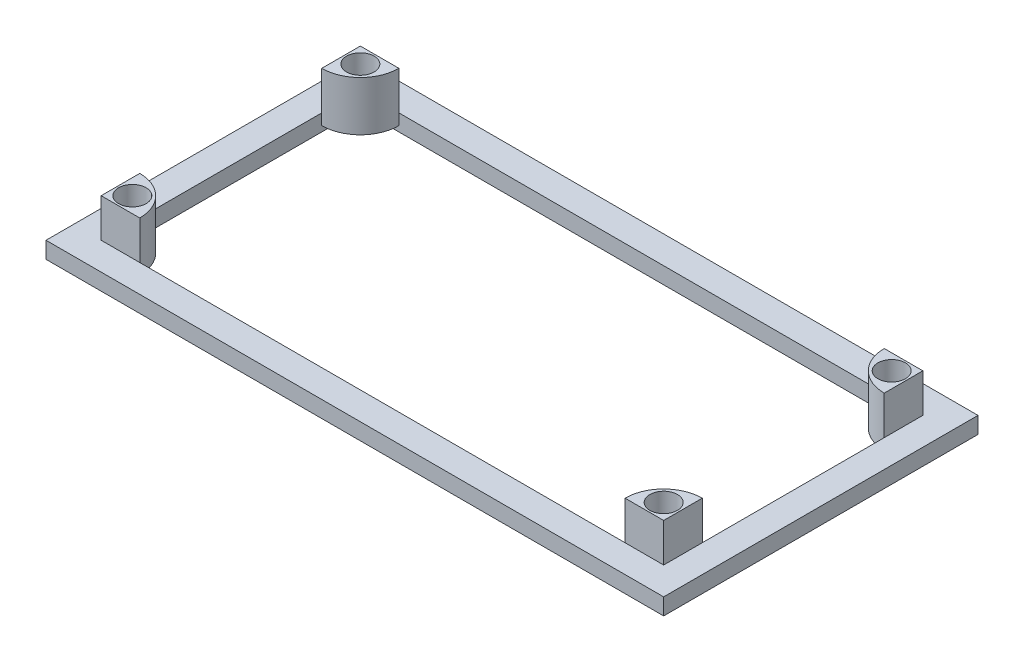
SolidWorks part; units mm, degrees
ref_plane "Front Plane" through (0, 0, 0) normal (0, 0, 1) x (1, 0, 0)
ref_plane "Top Plane" through (0, 0, 0) normal (0, 1, 0) x (1, 0, 0)
ref_plane "Right Plane" through (0, 0, 0) normal (1, 0, 0) x (0, 0, -1)
sketch "Sketch1" plane through (0, 0, 0) normal (0, 1, 0) x (1, 0, 0)
  line L1 (56, 28.5) -> (-56, 28.5)
  line L2 (56, 28.5) -> (56, -28.5)
  line L3 (56, -28.5) -> (-56, -28.5)
  line L4 (-56, 28.5) -> (-56, -28.5)
  line L5 (56, 28.5) -> (-56, -28.5) construction
  line L6 (56, -28.5) -> (-56, 28.5) construction
  line L7 (-51, -23.5) -> (51, -23.5)
  line L8 (-51, -23.5) -> (-51, 23.5)
  line L9 (-51, 23.5) -> (51, 23.5)
  line L10 (51, -23.5) -> (51, 23.5)
  line L11 (-51, -23.5) -> (51, 23.5) construction
  line L12 (-51, 23.5) -> (51, -23.5) construction
  point P0 (0, 0)
  point P6 (0, 0)
  dimension "D1" = 112
  dimension "D2" = 57
  dimension "D3" = 102
  dimension "D4" = 47
extrude "Boss-Extrude1" add sketch "Sketch1" along normal blind 3
sketch "Sketch2" plane through (0, 3, 0) normal (0, 1, 0) x (1, 0, 0)
  line L0 (-51, -23.5) -> (-44, -23.5)
  line L1 (-51, -23.5) -> (51, -23.5) construction
  line L2 (-51, 23.5) -> (-51, -23.5) construction
  line L3 (-51, -16.5) -> (-51, -23.5)
  line L4 (-51, -23.5) -> (-46.0503, -18.5503) construction
  arc A0 (-44, -23.5) -> (-51, -16.5) centre (-51, -23.5) ccw
  circle A1 centre (-48.1716, -20.6716) radius 2.5
  point P5 (-48.0211, -20.5211)
  point P12 (-43.7656, -16.2656)
  point P13 (-48.1886, -20.6886)
  point P14 (-48.1716, -20.6716)
  point P15 (-48.1716, -20.6716)
  point P16 (-48.1716, -20.6716)
  dimension "D1" = 7
  dimension "D2" = 5
  dimension "D3" = 3
extrude "Boss-Extrude2" add sketch "Sketch2" along normal blind 7 and the other way blind 2
mirror "Mirror1" about plane through (0, 0, 0) normal (0, 0, 1) of "Boss-Extrude2" second plane through (0, 0, 0) second plane normal (1, 0, 0)
